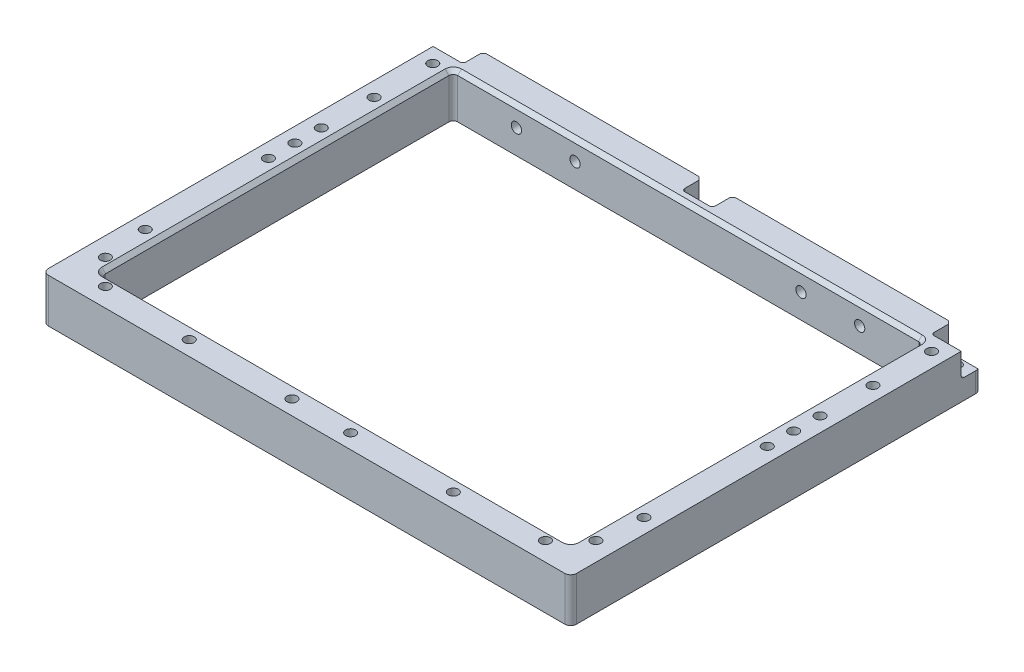
SolidWorks part; units mm, degrees
material "PLA"
ref_plane "Front Plane" through (0, 0, 0) normal (0, 0, 1) x (1, 0, 0)
ref_plane "Top Plane" through (0, 0, 0) normal (0, 1, 0) x (1, 0, 0)
ref_plane "Right Plane" through (0, 0, 0) normal (1, 0, 0) x (0, 0, -1)
sketch "Sketch1" plane through (0, 0, 0) normal (0, 1, 0) x (1, 0, 0)
  line L1 (-114.3, 88.9) -> (114.3, 88.9)
  line L2 (-114.3, 88.9) -> (-114.3, -88.9)
  line L3 (-114.3, -88.9) -> (114.3, -88.9)
  line L4 (114.3, 88.9) -> (114.3, -88.9)
  line L5 (-114.3, 88.9) -> (114.3, -88.9) construction
  line L6 (-114.3, -88.9) -> (114.3, 88.9) construction
  line L7 (-101.6, 76.2) -> (101.6, 76.2)
  line L8 (-101.6, 76.2) -> (-101.6, -76.2)
  line L9 (-101.6, -76.2) -> (101.6, -76.2)
  line L10 (101.6, 76.2) -> (101.6, -76.2)
  line L11 (-101.6, 76.2) -> (101.6, -76.2) construction
  line L12 (-101.6, -76.2) -> (101.6, 76.2) construction
  point P0 (0, 0)
  point P6 (0, 0)
  dimension "D1" = 177.8
  dimension "D2" = 152.4
  dimension "D3" = 228.6
  dimension "D4" = 203.2
extrude "Boss-Extrude1" add sketch "Sketch1" along normal blind 19.05
sketch "Sketch2" plane through (0, 0, -88.9) normal (0, 0, -1) x (-1, 0, 0)
  line L0 (114.3, 19.05) -> (114.3, 8.636)
  line L1 (114.3, 19.05) -> (114.3, 0) construction
  line L2 (114.3, 8.636) -> (101.346, 8.636)
  line L3 (101.346, 8.636) -> (101.346, 19.05)
  line L4 (-114.3, 19.05) -> (114.3, 19.05) construction
  line L5 (101.346, 19.05) -> (114.3, 19.05)
  line L6 (0, 0) -> (0, 19.05) construction
  line L7 (-6.604, 19.05) -> (6.604, 19.05)
  line L8 (6.604, 19.05) -> (6.604, 8.636)
  line L9 (6.604, 8.636) -> (-6.604, 8.636)
  line L11 (-6.604, 19.05) -> (-6.604, 8.636)
  line L12 (-101.346, 19.05) -> (-114.3, 19.05)
  line L13 (-101.346, 8.636) -> (-101.346, 19.05)
  line L14 (-114.3, 8.636) -> (-101.346, 8.636)
  line L15 (-114.3, 19.05) -> (-114.3, 8.636)
  point P16 (0, 8.636)
  dimension "D1" = 10.414
  dimension "D2" = 12.954
  dimension "D3" = 10.414
  dimension "D4" = 13.208
extrude "Cut-Extrude1" cut sketch "Sketch2" against normal blind 8.763
sketch "Sketch3" plane through (0, 8.636, 0) normal (0, 1, 0) x (1, 0, 0)
  line L0 (0, 88.9) -> (0, 80.137) construction
  line L1 (6.604, 88.9) -> (-6.604, 88.9) construction
  line L2 (-6.604, 80.137) -> (6.604, 80.137) construction
  line L3 (-107.823, 80.137) -> (-107.823, 88.9) construction
  line L4 (-114.3, 80.137) -> (-101.346, 80.137) construction
  line L5 (-101.346, 88.9) -> (-114.3, 88.9) construction
  circle A0 centre (-107.823, 84.5185) radius 2.159
  circle A1 centre (0, 84.5185) radius 2.159
  circle A2 centre (107.823, 84.5185) radius 2.159
  dimension "D1" = 4.318
  dimension "D2" = 4.318
extrude "Cut-Extrude2" cut sketch "Sketch3" against normal blind 6.35
fillet "Fillet2" radius 1.27 11 edges at (101.346, 8.636, -84.5185) (107.823, 8.636, -80.137) (-6.604, 8.636, -84.5185) (0, 8.636, -80.137) (6.604, 8.636, -84.5185) (-107.823, 8.636, -80.137) (-101.346, 8.636, -84.5185) (-101.346, 13.843, -80.137) (-6.604, 13.843, -80.137) (6.604, 13.843, -80.137) (101.346, 13.843, -80.137)
chamfer "Chamfer1" distance 1.27 angle 45 11 edges at (-108.458, 8.636, -88.9) (-101.718, 9.008, -88.9) (-101.346, 14.478, -88.9) (-6.604, 14.478, -88.9) (-6.232, 9.008, -88.9) (0, 8.636, -88.9) (6.232, 9.008, -88.9) (6.604, 14.478, -88.9) (108.458, 8.636, -88.9) (101.718, 9.008, -88.9) (101.346, 14.478, -88.9)
sketch "Sketch4" plane through (0, 0, -88.9) normal (0, 0, -1) x (-1, 0, 0)
  line L0 (0, 0) -> (0, 19.05) construction
  line L1 (-114.3, 0) -> (114.3, 0) construction
  line L2 (5.334, 19.05) -> (-5.334, 19.05) construction
  circle A0 centre (-20.32, 9.525) radius 1.905
  circle A1 centre (-81.28, 9.525) radius 1.905
  circle A2 centre (81.28, 9.525) radius 1.905
  circle A3 centre (20.32, 9.525) radius 1.905
  dimension "D1" = 3.81
  dimension "D2" = 3.81
  dimension "D3" = 20.32
  dimension "D4" = 81.28
  dimension "D5" = 9.525
  dimension "D6" = 9.525
extrude "Cut-Extrude3" cut sketch "Sketch4" against normal blind 7.112
sketch "Sketch5" plane through (0, 19.05, 0) normal (0, 1, 0) x (1, 0, 0)
  line L0 (-114.3, 80.137) -> (-114.3, -88.9) construction
  line L1 (-114.3, -88.9) -> (114.3, -88.9) construction
  line L2 (0, 0) -> (0, -50000) construction
  circle A0 centre (-95.25, -80.772) radius 2.159
  circle A1 centre (-106.172, -69.85) radius 2.159
  circle A2 centre (106.172, -69.85) radius 2.159
  circle A3 centre (95.25, -80.772) radius 2.159
  dimension "D1" = 4.318
  dimension "D2" = 4.318
  dimension "D3" = 8.128
  dimension "D4" = 8.128
  dimension "D5" = 19.05
  dimension "D6" = 19.05
extrude "Cut-Extrude4" cut sketch "Sketch5" against normal blind 7.112
fillet "Fillet3" radius 1.905 4 edges at (-101.6, 9.525, 76.2) (101.6, 9.525, 76.2) (101.6, 9.525, -76.2) (-101.6, 9.525, -76.2)
sketch "Sketch6" plane through (0, 19.05, 0) normal (0, 1, 0) x (1, 0, 0)
  line L0 (114.3, -88.9) -> (114.3, 80.137) construction
  line L1 (-99.695, -76.2) -> (99.695, -76.2) construction
  line L2 (101.6, -74.295) -> (101.6, 74.295) construction
  line L3 (0, 0) -> (0, -76.2) construction
  circle A0 centre (107.95, -50.8) radius 2.159
  circle A1 centre (107.95, 2.54) radius 2.159
  circle A2 centre (107.95, 13.97) radius 2.159
  circle A3 centre (107.95, 25.4) radius 2.159
  circle A4 centre (-107.95, 25.4) radius 2.159
  circle A5 centre (-107.95, 13.97) radius 2.159
  circle A6 centre (-107.95, 2.54) radius 2.159
  circle A7 centre (-107.95, -50.8) radius 2.159
  dimension "D1" = 4.318
  dimension "D4" = 4.318
  dimension "D5" = 4.318
  dimension "D6" = 4.318
  dimension "D2" = 6.35
  dimension "D7" = 78.74
  dimension "D8" = 90.17
  dimension "D9" = 101.6
  dimension "D10" = 6.35
  dimension "D11" = 6.35
  dimension "D12" = 6.35
extrude "Motor_Mount_Holes" cut sketch "Sketch6" against normal blind 7.112
chamfer "Chamfer2" distance 1.651 angle 45 8 edges at (-101.6, 19.05, 0) (-101.042, 19.05, 75.642) (-101.042, 19.05, -75.642) (0, 19.05, 76.2) (0, 19.05, -76.2) (101.042, 19.05, 75.642) (101.042, 19.05, -75.642) (101.6, 19.05, 0)
sketch "Sketch7" plane through (0, 19.05, 0) normal (0, 1, 0) x (1, 0, 0)
  line L0 (0, 0) -> (0, -88.9) construction
  line L1 (-114.3, -88.9) -> (114.3, -88.9) construction
  line L2 (-12.7, -76.2) -> (-12.7, -88.9) construction
  line L4 (-99.695, -76.2) -> (99.695, -76.2) construction
  circle A0 centre (-12.7, -82.55) radius 2.159
  circle A1 centre (12.7, -82.55) radius 2.159
  dimension "D1" = 4.318
  dimension "D2" = 12.7
extrude "RearBrace_MountHoles" cut sketch "Sketch7" against normal blind 7.112
sketch "Sketch8" plane through (0, 19.05, 0) normal (0, 1, 0) x (1, 0, 0)
  line L0 (114.3, 60.96) -> (101.6, 60.96) construction
  line L1 (114.3, -88.9) -> (114.3, 80.137) construction
  line L2 (101.6, -74.295) -> (101.6, 74.295) construction
  line L3 (107.95, 60.96) -> (107.95, 73.66) construction
  line L4 (-99.695, -76.2) -> (99.695, -76.2) construction
  line L5 (0, 0) -> (0, -88.9) construction
  line L6 (-114.3, -88.9) -> (114.3, -88.9) construction
  line L7 (-107.95, 60.96) -> (-107.95, 73.66) construction
  line L8 (-114.3, 60.96) -> (-101.6, 60.96) construction
  circle A0 centre (107.95, 73.66) radius 2.159
  circle A1 centre (107.95, 48.26) radius 2.159
  circle A2 centre (-107.95, 48.26) radius 2.159
  circle A3 centre (-107.95, 73.66) radius 2.159
  dimension "D1" = 4.318
  dimension "D2" = 25.4
  dimension "D3" = 137.16
extrude "SideBrace_MountHoles" cut sketch "Sketch8" against normal blind 7.112
sketch "Sketch9" plane through (0, 19.05, 0) normal (0, 1, 0) x (1, 0, 0)
  line L0 (0, -88.9) -> (0, -76.2) construction
  line L1 (-114.3, -88.9) -> (114.3, -88.9) construction
  line L2 (-99.695, -76.2) -> (99.695, -76.2) construction
  line L3 (0, -82.55) -> (-57.15, -82.55) construction
  circle A0 centre (-57.15, -82.55) radius 2.159
  circle A1 centre (57.15, -82.55) radius 2.159
  dimension "D1" = 4.318
  dimension "D2" = 114.3
extrude "BatteryMount_Holes" cut sketch "Sketch9" against normal blind 7.112
fillet "Fillet4" radius 2.54 4 edges at (-114.3, 3.683, -88.9) (114.3, 3.683, -88.9) (-114.3, 9.525, 88.9) (114.3, 9.525, 88.9)
sketch "Sketch10" plane through (0, 0, -76.2) normal (0, 0, 1) x (1, 0, 0)
  line L0 (0, 0) -> (0, 50000) construction
  line L1 (-111.76, 0) -> (111.76, 0) construction
  line L2 (101.6, 17.399) -> (101.6, 0) construction
  line L3 (48.895, 10.541) -> (74.295, 10.541) construction
  line L4 (99.695, 0) -> (-99.695, 0) construction
  line L5 (-48.895, 10.541) -> (-74.295, 10.541) construction
  circle A0 centre (48.895, 10.541) radius 2.2225
  circle A1 centre (74.295, 10.541) radius 2.2225
  circle A2 centre (-74.295, 10.541) radius 2.2225
  circle A3 centre (-48.895, 10.541) radius 2.2225
  point P4 (0, 0)
  dimension "D3" = 4.445
  dimension "D1" = 25.4
  dimension "D2" = 27.305
  dimension "D4" = 10.541
extrude "Cut-Extrude5" cut sketch "Sketch10" against normal blind 5.08
equation "\"D2@Sketch3\"=\"D1@Sketch3\""
equation "\"D2@Sketch5\"=\"D1@Sketch5\""
equation "\"D4@Sketch6\"=\"D1@Sketch6\""
equation "\"D5@Sketch6\"=\"D1@Sketch6\""
equation "\"D6@Sketch6\"=\"D1@Sketch6\""
equation "\"D10@Sketch6\"=\"D2@Sketch6\""
equation "\"D11@Sketch6\"=\"D2@Sketch6\""
equation "\"D12@Sketch6\"=\"D2@Sketch6\""
equation "\"D1@Sketch2\"=\"D3@Sketch2\""
